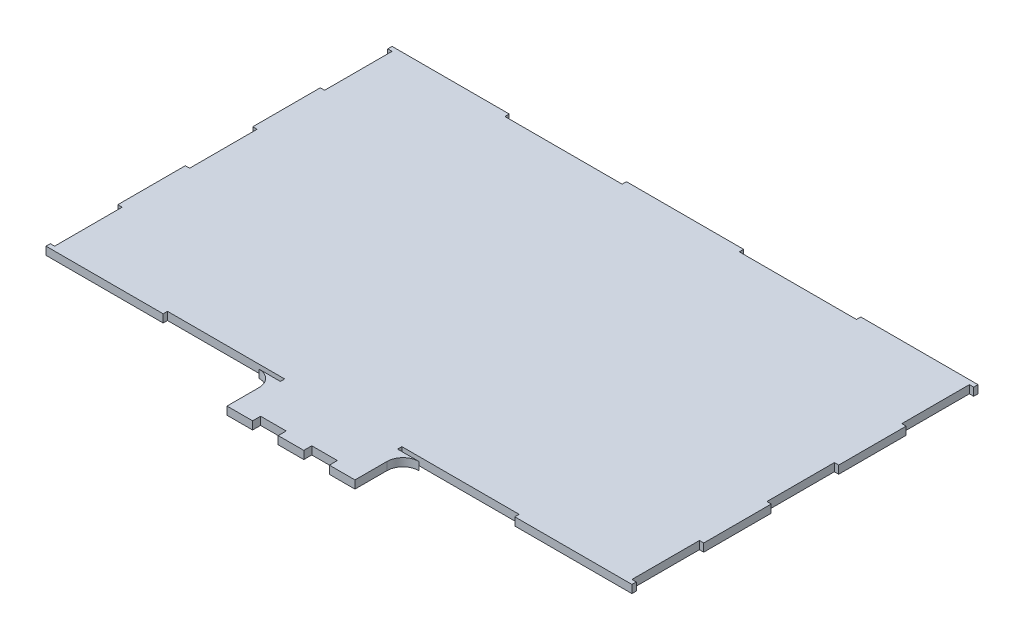
SolidWorks part; units mm, degrees
ref_plane "Front Plane" through (0, 0, 0) normal (0, 0, 1) x (1, 0, 0)
ref_plane "Top Plane" through (0, 0, 0) normal (0, 1, 0) x (1, 0, 0)
ref_plane "Right Plane" through (0, 0, 0) normal (1, 0, 0) x (0, 0, -1)
sketch "Sketch1" plane through (0, 0, 0) normal (0, 1, 0) x (1, 0, 0)
  line L0 (-183.2, 108.2) -> (-109.92, 108.2)
  line L1 (-109.92, 105.5) -> (-36.64, 105.5)
  line L4 (180.5, 105.5) -> (180.5, 63.3)
  line L5 (183.2, 108.2) -> (183.2, 105.5)
  line L8 (183.2, 63.3) -> (183.2, 21.1)
  line L9 (183.2, 108.2) -> (183.2, -108.2) construction
  line L10 (180.5, -105.5) -> (183.2, -105.5)
  line L11 (180.5, 105.5) -> (183.2, 105.5)
  line L13 (180.5, 105.5) -> (180.5, -105.5) construction
  line L14 (180.5, 21.1) -> (180.5, -21.1)
  line L16 (180.5, -63.3) -> (180.5, -105.5)
  line L18 (-180.5, 105.5) -> (-180.5, -105.5) construction
  line L23 (-183.2, 108.2) -> (183.2, 108.2) construction
  line L24 (-36.64, 108.2) -> (36.64, 108.2)
  line L26 (109.92, 108.2) -> (183.2, 108.2)
  line L27 (-109.92, 108.2) -> (-109.92, 105.5)
  line L28 (-36.64, 108.2) -> (-36.64, 105.5)
  line L29 (36.64, 108.2) -> (36.64, 105.5)
  line L30 (109.92, 108.2) -> (109.92, 105.5)
  line L31 (-180.5, 105.5) -> (180.5, 105.5) construction
  line L32 (36.64, 105.5) -> (109.92, 105.5)
  line L33 (-183.2, -108.2) -> (183.2, -108.2) construction
  line L34 (-180.5, -105.5) -> (180.5, -105.5) construction
  line L35 (180.5, -21.1) -> (183.2, -21.1)
  line L36 (109.92, -108.2) -> (183.2, -108.2)
  line L37 (109.92, -108.2) -> (109.92, -105.5)
  line L38 (36.64, -105.5) -> (109.92, -105.5)
  line L39 (36.64, -108.2) -> (36.64, -105.5)
  line L41 (-36.64, -108.2) -> (-36.64, -105.5)
  line L42 (-109.92, -105.5) -> (-36.64, -105.5)
  line L43 (-109.92, -108.2) -> (-109.92, -105.5)
  line L44 (-183.2, -108.2) -> (-109.92, -108.2)
  line L45 (180.5, -63.3) -> (183.2, -63.3)
  line L46 (180.5, 21.1) -> (183.2, 21.1)
  line L47 (180.5, 63.3) -> (183.2, 63.3)
  line L48 (183.2, -21.1) -> (183.2, -63.3)
  line L49 (-183.2, 108.2) -> (-183.2, -108.2) construction
  line L50 (183.2, -105.5) -> (183.2, -108.2)
  line L51 (-40, -118.2) -> (-40, -138.2)
  line L52 (-183.2, -105.5) -> (-183.2, -108.2)
  line L53 (-180.5, -105.5) -> (-183.2, -105.5)
  line L54 (-180.5, -63.3) -> (-180.5, -105.5)
  line L55 (-180.5, -63.3) -> (-183.2, -63.3)
  line L56 (-183.2, -21.1) -> (-183.2, -63.3)
  line L57 (-180.5, -21.1) -> (-183.2, -21.1)
  line L58 (-180.5, 21.1) -> (-180.5, -21.1)
  line L59 (-180.5, 21.1) -> (-183.2, 21.1)
  line L60 (-183.2, 63.3) -> (-183.2, 21.1)
  line L61 (-180.5, 63.3) -> (-183.2, 63.3)
  line L62 (-180.5, 105.5) -> (-180.5, 63.3)
  line L63 (-183.2, 108.2) -> (-183.2, 105.5)
  line L64 (-180.5, 105.5) -> (-183.2, 105.5)
  line L65 (-36.64, -108.2) -> (-40, -108.2)
  line L66 (36.64, -108.2) -> (40, -108.2)
  line L67 (40, -118.2) -> (40, -138.2)
  line L70 (-40, -138.2) -> (-24, -138.2)
  line L71 (24, -133.2) -> (8, -133.2)
  line L73 (50, -108.2) -> (40, -108.2)
  line L74 (-40, -108.2) -> (-50, -108.2)
  line L75 (-8, -138.2) -> (8, -138.2)
  line L77 (24, -138.2) -> (40, -138.2)
  line L78 (-24, -138.2) -> (-24, -133.2)
  line L79 (-8, -138.2) -> (-8, -133.2)
  line L80 (8, -138.2) -> (8, -133.2)
  line L81 (24, -138.2) -> (24, -133.2)
  line L82 (-8, -133.2) -> (-24, -133.2)
  arc A0 (-50, -108.2) -> (-40, -118.2) centre (-50, -118.2) cw
  arc A1 (40, -118.2) -> (50, -108.2) centre (50, -118.2) cw
  point P0 (0, 0)
  dimension "D2" = 10
  dimension "D3" = 10
  dimension "D1" = 2.7
extrude "Boss-Extrude1" add sketch "Sketch1" along normal blind 5
